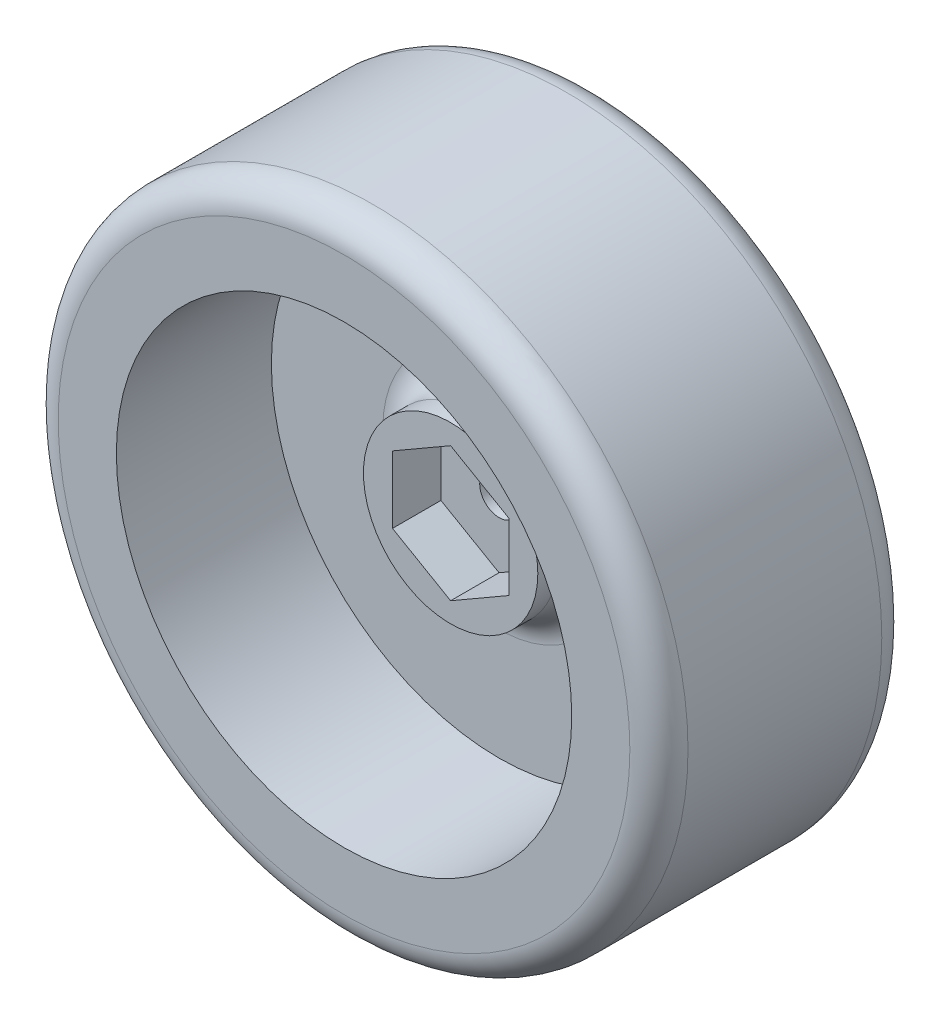
SolidWorks part; units mm, degrees
ref_plane "Front Plane" through (0, 0, 0) normal (0, 0, 1) x (1, 0, 0)
ref_plane "Top Plane" through (0, 0, 0) normal (0, 1, 0) x (1, 0, 0)
ref_plane "Right Plane" through (0, 0, 0) normal (1, 0, 0) x (0, 0, -1)
sketch "Sketch1" plane through (0, 0, 0) normal (0, 0, 1) x (1, 0, 0)
  circle A0 centre (0, 0) radius 32.5
  circle A1 centre (0, 0) radius 2
  dimension "D1" = 65
  dimension "D2" = 4
extrude "Boss-Extrude1" add sketch "Sketch1" along normal blind 26
fillet "Fillet1" radius 3 2 edges at (32.5, 0, 0) (32.5, 0, 26)
sketch "Sketch2" plane through (0, 0, 26) normal (0, 0, 1) x (1, 0, 0)
  circle A0 centre (0, 0) radius 23.5
  dimension "D1" = 47
extrude "Cut-Extrude1" cut sketch "Sketch2" against normal blind 16
sketch "Sketch3" plane through (0, 0, 10) normal (0, 0, 1) x (1, 0, 0)
  line L0 (0, 0) -> (50000, 0) construction
  line L1 (0, 0) -> (0, 50000) construction
  line L2 (-6, -3.4641) -> (-6, 3.4641)
  line L3 (6, -3.4641) -> (6, 3.4641)
  line L4 (-6, 3.4641) -> (0, 6.9282)
  line L5 (-6, -3.4641) -> (0, -6.9282)
  line L6 (6, -3.4641) -> (0, -6.9282)
  line L7 (6, 3.4641) -> (0, 6.9282)
  circle A0 centre (0, 0) radius 9
  point P10 (-6, 0)
  point P15 (-0.2486, -4.7845)
  point P16 (0, 0)
  dimension "D4" = 18
  dimension "D1" = 12
  dimension "D2" = 12
  dimension "D3" = 12
extrude "Boss-Extrude2" add sketch "Sketch3" along normal blind 5
sketch "Sketch4" plane through (0, 0, 0) normal (0, 0, -1) x (-1, 0, 0)
  circle A0 centre (0, 0) radius 7.5
  dimension "D1" = 15
extrude "Cut-Extrude2" cut sketch "Sketch4" against normal blind 2
sketch "Sketch5" plane through (0, 0, 2) normal (0, 0, -1) x (-1, 0, 0)
  circle A0 centre (0, 0) radius 5
  dimension "D1" = 10
extrude "Cut-Extrude3" cut sketch "Sketch5" against normal blind 4
fillet "Fillet2" radius 3 1 edges at (9, 0, 10)
